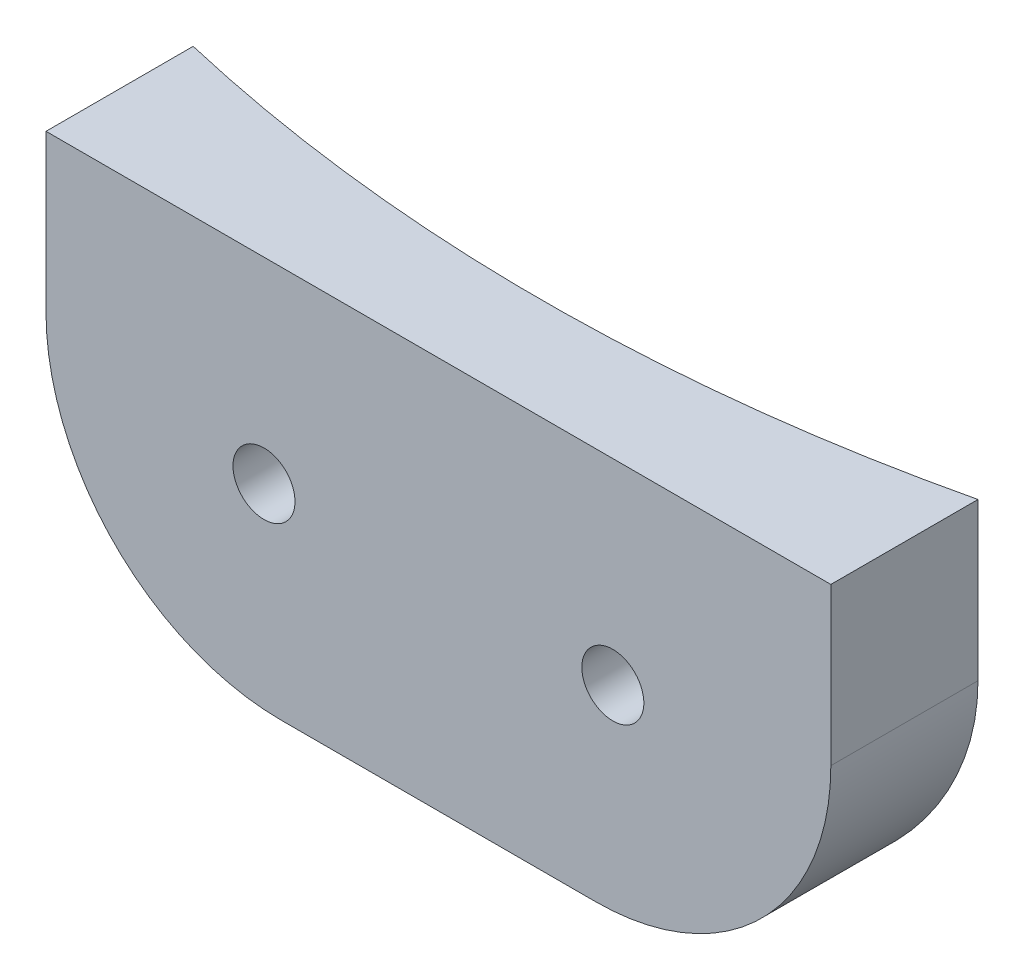
SolidWorks part; units mm, degrees
material "6061 Alloy"
ref_plane "Front Plane" through (0, 0, 0) normal (0, 0, 1) x (1, 0, 0)
ref_plane "Top Plane" through (0, 0, 0) normal (0, 1, 0) x (1, 0, 0)
ref_plane "Right Plane" through (0, 0, 0) normal (1, 0, 0) x (0, 0, -1)
sketch "Sketch1" plane through (0, 0, 0) normal (0, 1, 0) x (1, 0, 0)
  line L0 (-12.7, -54.0916) -> (-12.7, -57.3481)
  line L1 (12.7, -54.0916) -> (12.7, -57.3481)
  line L2 (-12.7, -58.8541) -> (12.7, -58.8541)
  line L3 (-12.7, -57.3481) -> (-12.7, -58.8541)
  line L4 (12.7, -57.3481) -> (12.7, -58.8541)
  circle A0 centre (0, 0) radius 55.5625
  circle A1 centre (0, 0) radius 58.7375
  dimension "D1" = 111.125
  dimension "D3" = 12.7
  dimension "D4" = 12.7
  dimension "D5" = 4.7625
  dimension "D2" = 3.175
extrude "Boss-Extrude1" add sketch "Sketch1" along normal blind 12.7 contours L0 A1 L1 A0 | A1 L3 L2 | A1 L2 L4 region at (0, 0, 56.6725) region at (0, 0, 58.7629)
sketch "Sketch2" plane through (0, 0, 0) normal (0, 0, 1) x (1, 0, 0)
  line L0 (0, 12.7) -> (0, 0) construction
  line L5 (-12.7, 0) -> (12.7, 0)
  line L6 (12.7, 0) -> (12.7, 12.7)
  line L7 (12.7, 12.7) -> (-12.7, 12.7)
  line L12 (-12.7, 12.7) -> (-12.7, 0)
  line L13 (-12.7, 0) -> (12.7, 0)
  line L14 (12.7, 0) -> (12.7, 12.7)
  line L15 (12.7, 12.7) -> (-12.7, 12.7)
  line L16 (-12.7, 12.7) -> (-12.7, 0)
  circle A0 centre (-5.6444, 6.35) radius 1.0033
  dimension "D6" = 2.0066
  dimension "D5" = 5.6444
  dimension "D2" = 6.35
extrude "Cut-Extrude1" cut sketch "Sketch2" along normal up to surface (58.8541 mm away) contours A0 up to face at (0, 6.35, 58.8541)
mirror "Mirror1" about plane through (0, 0, 0) normal (1, 0, 0) of "Cut-Extrude1"
fillet "Fillet1" radius 7.62 2 edges at (-12.7, 0, 56.4729) (12.7, 0, 56.4729)
equation "\"Middle Coupler Inner Daimeter\"= 3.875in"
equation "\"Middle Coupler  Wall Thickness\" = 0.25in"
equation "\"Middle Coupler Bottom Thickness\"= 0.2in"
equation "\"Bearing Rail Offset\"= 0.45in"
equation "\"3-56 UNF Tap\"= 0.089in"
equation "\"3-56 UNF Clearance\"= 0.104in"
equation "\"Ball Bearing Distance\"= 0.03in"
equation "\"TCA Outer Diameter\" = 6in"
equation "\"D1@Sketch1\"=\"Middle Coupler Inner Daimeter\"+0.5"
equation "\"D2@Sketch1\"=1/8"
equation "\"D3@Sketch1\"=0.5"
equation "\"D4@Sketch1\"=\"D3@Sketch1\""
equation "\"D6@Sketch2\"=\"3-48 Tap\""
equation "\"Interstage Aeroframe Wall Thickness\" = 0.072in"
equation "\"Compression Spring OD\"= 0.42in"
equation "\"10-24 Tap\"= 0.157in"
equation "\"10-24 Clearance\"= 0.196in"
equation "\"Lower Stage Fuselage Wall Thickness\" = 0.25in"
equation "\"6-32 Tap\" = 0.107in"
equation "\"1/4-20 Tap\" = 0.201in"
equation "\"3-48 Tap\"= 0.079in"
equation "\"3-48 Clearance\" = 0.104in"
equation "\"6-32 Clearance\" = 0.144"
equation "\"12-24 Tap\" = 0.177in"
equation "\"D5@Sketch1\"=3/16"
